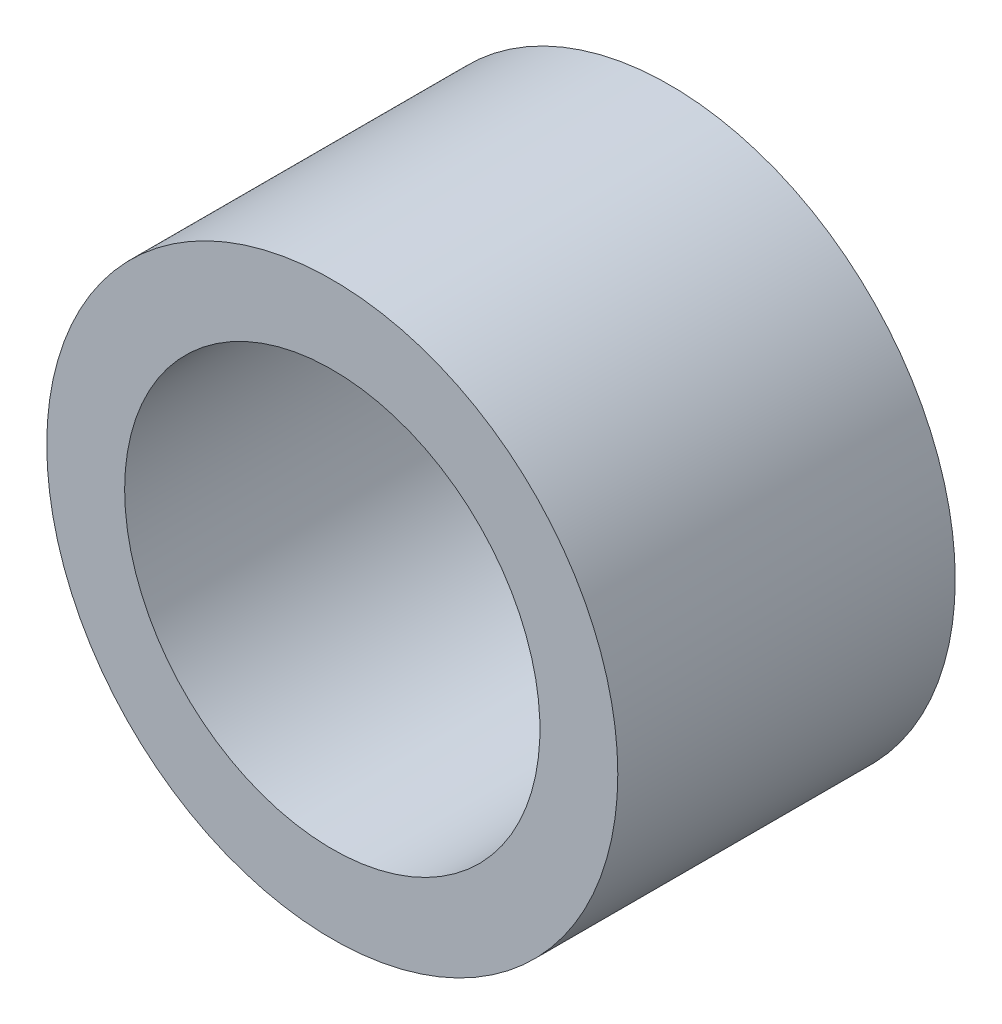
SolidWorks part; units mm, degrees
ref_plane "Front Plane" through (0, 0, 0) normal (0, 0, 1) x (1, 0, 0)
ref_plane "Top Plane" through (0, 0, 0) normal (0, 1, 0) x (1, 0, 0)
ref_plane "Right Plane" through (0, 0, 0) normal (1, 0, 0) x (0, 0, -1)
ref_plane "Plane1" through (0, 0, 10.6199) normal (0, 0, -1) x (-1, 0, 0)
sketch "Sketch1" plane through (0, 0, 10.6199) normal (0, 0, -1) x (-1, 0, 0)
  circle A0 centre (41.5529, -51.3213) radius 5.5
  circle A1 centre (41.5529, -51.3213) radius 16.8 construction
  circle A2 centre (41.5529, -51.3213) radius 4
  dimension "D1" = 11
  dimension "D2" = 8
extrude "Boss-Extrude1" add sketch "Sketch1" along normal up to surface (6.5 mm away)
